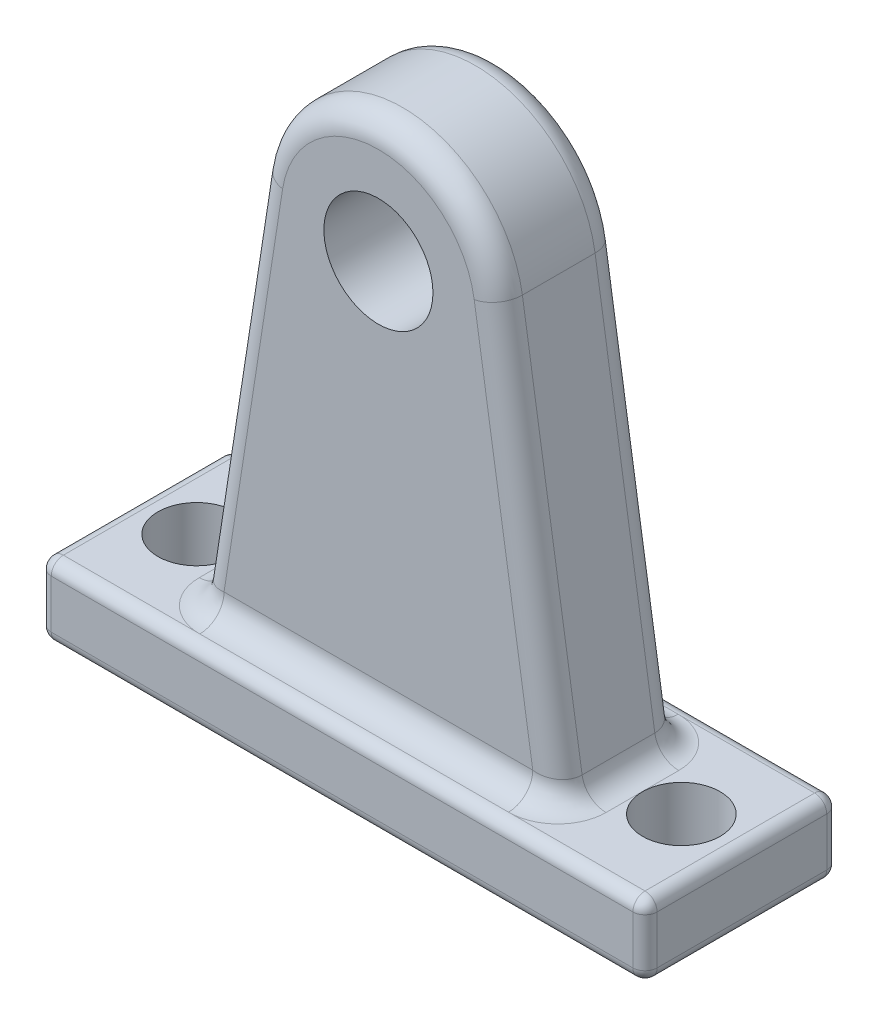
SolidWorks part; units mm, degrees
ref_plane "前视基准面" through (0, 0, 0) normal (0, 0, 1) x (1, 0, 0)
ref_plane "上视基准面" through (0, 0, 0) normal (0, 1, 0) x (1, 0, 0)
ref_plane "右视基准面" through (0, 0, 0) normal (1, 0, 0) x (0, 0, -1)
other "Configuration Table"
sketch "草图2" plane through (0, 0, 0) normal (0, 0, 1) x (1, 0, 0)
  line L0 (-8, 0) -> (8, 0)
  line L1 (-8, 0) -> (-4.9412, 19.7647)
  line L2 (4.9412, 19.7647) -> (8, 0)
  arc A0 (4.9412, 19.7647) -> (-4.9412, 19.7647) centre (0, 19) ccw
  circle A1 centre (0, 19) radius 2.25
  point P4 (0, 0)
  dimension "D1" = 10
  dimension "D4" = 4.5
  dimension "D2" = 19
  dimension "D3" = 16
extrude "凸台-拉伸1" add sketch "草图2" along normal mid plane 5
sketch "草图4" plane through (0, 0, 0) normal (0, -1, 0) x (1, 0, 0)
  line L1 (-12.5, -4) -> (12.5, -4)
  line L2 (-12.5, -4) -> (-12.5, 4)
  line L3 (-12.5, 4) -> (12.5, 4)
  line L4 (12.5, -4) -> (12.5, 4)
  line L5 (-12.5, -4) -> (12.5, 4) construction
  line L6 (-12.5, 4) -> (12.5, -4) construction
  point P0 (0, 0)
  dimension "D1" = 8
  dimension "D2" = 25
extrude "凸台-拉伸2" add sketch "草图4" against normal blind 3
sketch "草图5" plane through (0, 3, 0) normal (0, 1, 0) x (1, 0, 0)
  circle A0 centre (-10, 0) radius 1.6
  point P2 (0, 0)
  dimension "D2" = 3.2
  dimension "D1" = 10
extrude "切除-拉伸1" cut sketch "草图5" against normal blind 3
mirror "镜向1" about plane through (0, 0, 0) normal (1, 0, 0) of "切除-拉伸1"
fillet "圆角1" radius 1 10 edges at (0, 3, 2.5) (0, 3, -2.5) (0, 24, 2.5) (0, 24, -2.5) (6.2384, 11.3824, -2.5) (7.5357, 3, 0) (6.2384, 11.3824, 2.5) (-6.2384, 11.3824, 2.5) (-7.5357, 3, 0) (-6.2384, 11.3824, -2.5)
fillet "圆角2" radius 0.5 12 edges at (12.5, 3, 0) (12.5, 0, 0) (12.5, 1.5, -4) (0, 3, -4) (0, 0, -4) (-12.5, 1.5, -4) (-12.5, 3, 0) (-12.5, 0, 0) (-12.5, 1.5, 4) (0, 3, 4) (12.5, 1.5, 4) (0, 0, 4)
